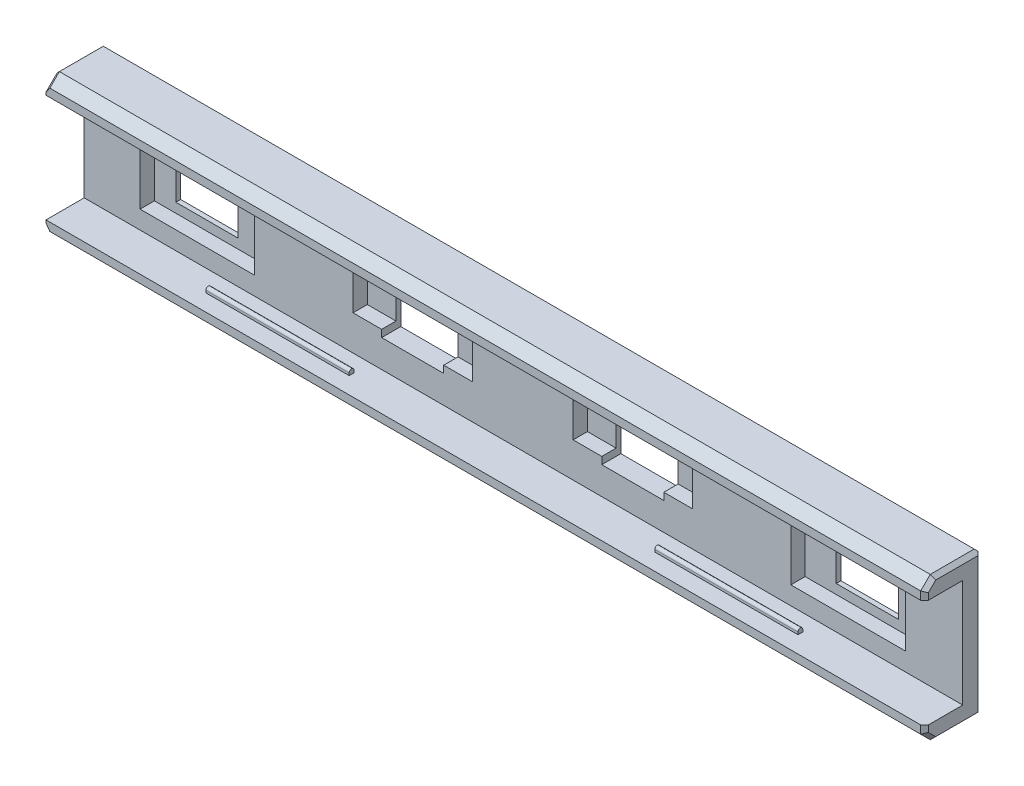
SolidWorks part; units mm, degrees
ref_plane "Front Plane" through (0, 0, 0) normal (0, 0, 1) x (1, 0, 0)
ref_plane "Top Plane" through (0, 0, 0) normal (0, 1, 0) x (1, 0, 0)
ref_plane "Right Plane" through (0, 0, 0) normal (1, 0, 0) x (0, 0, -1)
sketch "Sketch1" plane through (0, 0, 0) normal (0, 0, 1) x (1, 0, 0)
  line L1 (-45.75, 25.6543) -> (46.25, 25.6543)
  line L2 (-45.75, 25.6543) -> (-45.75, 10.6543)
  line L3 (-45.75, 10.6543) -> (46.25, 10.6543)
  line L4 (46.25, 25.6543) -> (46.25, 10.6543)
  dimension "D1" = 92
  dimension "D2" = 15
extrude "Boss-Extrude1" add sketch "Sketch1" along normal blind 6
sketch "Sketch2" plane through (0, 0, 6) normal (0, 0, 1) x (1, 0, 0)
  line L0 (-45.75, 25.6543) -> (-45.75, 10.6543) construction
  line L1 (-37.65, 20.9043) -> (-31.15, 20.9043)
  line L2 (-37.65, 20.9043) -> (-37.65, 15.4043)
  line L3 (-37.65, 15.4043) -> (-31.15, 15.4043)
  line L4 (-31.15, 20.9043) -> (-31.15, 15.4043)
  line L5 (46.25, 25.6543) -> (-45.75, 25.6543) construction
  dimension "D1" = 6.5
  dimension "D2" = 5.5
  dimension "D3" = 8.1
  dimension "D4" = 4.75
extrude "Cut-Extrude1" cut sketch "Sketch2" against normal through all both and the other way through all
sketch "Sketch3" plane through (0, 0, 6) normal (0, 0, 1) x (1, 0, 0)
  line L0 (-31.15, 15.4043) -> (-31.15, 20.9043) construction
  line L1 (-14.6, 20.9043) -> (-8.1, 20.9043)
  line L2 (-14.6, 20.9043) -> (-14.6, 15.4043)
  line L3 (-14.6, 15.4043) -> (-8.1, 15.4043)
  line L4 (-8.1, 20.9043) -> (-8.1, 15.4043)
  dimension "D1" = 6.5
  dimension "D2" = 5.5
  dimension "D3" = 16.55
extrude "Cut-Extrude2" cut sketch "Sketch3" against normal through all both and the other way through all
sketch "Sketch4" plane through (0, 0, 6) normal (0, 0, 1) x (1, 0, 0)
  line L0 (-8.1, 15.4043) -> (-8.1, 20.9043) construction
  line L1 (8.45, 20.9043) -> (14.95, 20.9043)
  line L2 (8.45, 20.9043) -> (8.45, 15.4043)
  line L3 (8.45, 15.4043) -> (14.95, 15.4043)
  line L4 (14.95, 20.9043) -> (14.95, 15.4043)
  line L5 (-45.75, 10.6543) -> (46.25, 10.6543) construction
  dimension "D1" = 6.5
  dimension "D2" = 5.5
  dimension "D3" = 16.55
  dimension "D4" = 4.75
extrude "Cut-Extrude3" cut sketch "Sketch4" against normal through all both and the other way through all
sketch "Sketch5" plane through (0, 0, 6) normal (0, 0, 1) x (1, 0, 0)
  line L0 (14.95, 15.4043) -> (14.95, 20.9043) construction
  line L1 (31.5, 20.9043) -> (38, 20.9043)
  line L2 (31.5, 20.9043) -> (31.5, 15.4043)
  line L3 (31.5, 15.4043) -> (38, 15.4043)
  line L4 (38, 20.9043) -> (38, 15.4043)
  dimension "D1" = 6.5
  dimension "D2" = 5.5
  dimension "D3" = 16.55
extrude "Cut-Extrude4" cut sketch "Sketch5" against normal through all both and the other way through all
sketch "Sketch8" plane through (0, 0, 6) normal (0, 0, 1) x (1, 0, 0)
  line L0 (-45.75, 25.6543) -> (-45.75, 10.6543) construction
  line L1 (46.25, 10.6543) -> (46.25, 25.6543) construction
  line L2 (-45.75, 23.8043) -> (46.25, 23.8043)
  line L3 (-45.75, 23.8043) -> (-45.75, 12.5043)
  line L4 (-45.75, 12.5043) -> (46.25, 12.5043)
  line L5 (46.25, 23.8043) -> (46.25, 12.5043)
  line L6 (46.25, 25.6543) -> (-45.75, 25.6543) construction
  dimension "D1" = 11.3
  dimension "D2" = 1.85
extrude "Cut-Extrude5" cut sketch "Sketch8" against normal blind 4 and the other way through all
sketch "Sketch9" plane through (0, 0, 2) normal (0, 0, 1) x (1, 0, 0)
  line L2 (46.25, 12.5043) -> (46.25, 23.8043) construction
  line L3 (28.25, 21.9043) -> (40.25, 21.9043)
  line L4 (28.25, 21.9043) -> (28.25, 14.4043)
  line L5 (28.25, 14.4043) -> (40.25, 14.4043)
  line L6 (40.25, 21.9043) -> (40.25, 14.4043)
  line L7 (-45.75, 12.5043) -> (46.25, 12.5043) construction
  line L11 (46.25, 12.5043) -> (-45.75, 12.5043) construction
  line L12 (-39.9, 21.9043) -> (-27.9, 21.9043)
  line L13 (-39.9, 21.9043) -> (-39.9, 14.4043)
  line L14 (-39.9, 14.4043) -> (-27.9, 14.4043)
  line L15 (-27.9, 21.9043) -> (-27.9, 14.4043)
  line L16 (-37.65, 15.4043) -> (-37.65, 20.9043) construction
  dimension "D1" = 6
  dimension "D2" = 12
  dimension "D3" = 7.5
  dimension "D4" = 1.9
  dimension "D5" = 12
  dimension "D6" = 7.5
  dimension "D7" = 1.9
  dimension "D8" = 2.25
extrude "Cut-Extrude6" cut sketch "Sketch9" against normal blind 1.5
sketch "Sketch10" plane through (0, 0, 2) normal (0, 0, 1) x (1, 0, 0)
  line L1 (5.45, 20.1543) -> (17.95, 20.1543)
  line L2 (5.45, 20.1543) -> (5.45, 16.1543)
  line L3 (5.45, 16.1543) -> (17.95, 16.1543)
  line L4 (17.95, 20.1543) -> (17.95, 16.1543)
  line L5 (-17.6, 20.1543) -> (-5.1, 20.1543)
  line L6 (-17.6, 20.1543) -> (-17.6, 16.1543)
  line L7 (-17.6, 16.1543) -> (-5.1, 16.1543)
  line L8 (-5.1, 20.1543) -> (-5.1, 16.1543)
  line L9 (-14.6, 15.4043) -> (-14.6, 20.9043) construction
  line L10 (-8.1, 20.9043) -> (-8.1, 15.4043) construction
  line L11 (-8.1, 15.4043) -> (-14.6, 15.4043) construction
  line L13 (8.45, 15.4043) -> (8.45, 20.9043) construction
  line L15 (14.95, 15.4043) -> (8.45, 15.4043) construction
  dimension "D1" = 3
  dimension "D2" = 3
  dimension "D3" = 4
  dimension "D4" = 0.75
  dimension "D5" = 12.5
  dimension "D6" = 3
  dimension "D7" = 4
  dimension "D8" = 0.75
extrude "Cut-Extrude7" cut sketch "Sketch10" against normal blind 1.5
sketch "Sketch12" plane through (46.25, 0, 0) normal (1, 0, 0) x (0, 0, -1)
  line L0 (-6, 25.6543) -> (-6, 24.6543)
  line L1 (-6, 23.8043) -> (-6, 25.6543) construction
  line L2 (-6, 24.6543) -> (-5, 25.6543)
  line L3 (-6, 25.6543) -> (0, 25.6543) construction
  line L4 (-5, 25.6543) -> (-6, 25.6543)
  line L5 (-6, 10.6543) -> (-5, 10.6543)
  line L6 (-6, 10.6543) -> (0, 10.6543) construction
  line L7 (-5, 10.6543) -> (-6, 11.6543)
  line L8 (-6, 10.6543) -> (-6, 12.5043) construction
  line L9 (-6, 11.6543) -> (-6, 10.6543)
  dimension "D1" = 1
  dimension "D2" = 1
  dimension "D3" = 1
extrude "Cut-Extrude8" cut sketch "Sketch12" against normal blind 92
sketch "Sketch13" plane through (0, 0, 0) normal (0, 0, -1) x (-1, 0, 0)
  line L0 (45.75, 25.6543) -> (45.75, 10.6543) construction
  line L1 (43.25, 23.1543) -> (43.75, 23.1543)
  line L2 (43.25, 23.1543) -> (43.25, 13.1543)
  line L3 (43.25, 13.1543) -> (43.75, 13.1543)
  line L4 (43.75, 23.1543) -> (43.75, 13.1543)
  line L5 (-46.25, 25.6543) -> (45.75, 25.6543) construction
  dimension "D1" = 2
  dimension "D2" = 0.5
  dimension "D3" = 10
  dimension "D4" = 2.5
extrude "Cut-Extrude9" cut sketch "Sketch13" against normal blind 0.6
fillet "Fillet1" radius 0.25 1 edges at (-43.75, 18.1543, 0)
fillet "Fillet2" radius 0.25 4 edges at (-43.5, 23.1543, 0.6) (-43.75, 18.1543, 0.6) (-43.5, 13.1543, 0.6) (-43.25, 18.1543, 0.6)
sketch "Sketch16" plane through (0, 23.8043, 0) normal (0, -1, 0) x (1, 0, 0)
  line L0 (-45.75, 6) -> (46.25, 6) construction
  line L1 (-15.75, 4.25) -> (-30.75, 4.25)
  line L2 (-15.75, 4.25) -> (-15.75, 3.75)
  line L3 (-15.75, 3.75) -> (-30.75, 3.75)
  line L4 (-30.75, 4.25) -> (-30.75, 3.75)
  line L5 (-45.75, 6) -> (-45.75, 2) construction
  dimension "D1" = 15
  dimension "D2" = 0.5
  dimension "D3" = 1.75
  dimension "D4" = 15
extrude "Boss-Extrude2" add sketch "Sketch16" along normal blind 0.75
fillet "Fillet3" radius 0.5 1 edges at (-23.25, 23.0543, 4.25)
fillet "Fillet4" radius 0.25 1 edges at (-23.25, 23.0543, 3.75)
sketch "Sketch17" plane through (0, 12.5043, 0) normal (0, 1, 0) x (1, 0, 0)
  line L0 (-45.75, -6) -> (-45.75, -2) construction
  line L1 (-15.75, -3.75) -> (-30.75, -3.75)
  line L2 (-15.75, -3.75) -> (-15.75, -4.25)
  line L3 (-15.75, -4.25) -> (-30.75, -4.25)
  line L4 (-30.75, -3.75) -> (-30.75, -4.25)
  line L5 (46.25, -6) -> (-45.75, -6) construction
  dimension "D1" = 15
  dimension "D2" = 0.5
  dimension "D3" = 15
  dimension "D4" = 1.75
extrude "Boss-Extrude3" add sketch "Sketch17" along normal blind 0.75
fillet "Fillet5" radius 0.5 1 edges at (-23.25, 13.2543, 4.25)
fillet "Fillet6" radius 0.25 1 edges at (-23.25, 13.2543, 3.75)
pattern_linear "LPattern1" count 2 spacing 47 along (1, 0, 0) of "Boss-Extrude3"
pattern_linear "LPattern2" count 2 spacing 47 along (1, 0, 0) of "Boss-Extrude2"
fillet "Fillet7" radius 0.5 1 edges at (23.75, 23.0543, 4.25)
fillet "Fillet8" radius 0.25 1 edges at (23.75, 23.0543, 3.75)
fillet "Fillet9" radius 0.5 1 edges at (23.75, 13.2543, 4.25)
fillet "Fillet10" radius 0.25 1 edges at (23.75, 13.2543, 3.75)
chamfer "Chamfer1" distance 0.4 angle 45 2 edges at (0.25, 10.6543, 0) (0.25, 25.6543, 0)
chamfer "Chamfer2" distance 0.4 angle 45 2 edges at (46.25, 18.1543, 0) (-45.75, 18.1543, 0)
chamfer "Chamfer3" distance 0.4 angle 45 2 edges at (-45.75, 10.6543, 2.7) (-45.75, 25.6543, 2.7)
chamfer "Chamfer4" distance 0.4 angle 45 2 edges at (-45.75, 11.3543, 5.7) (-45.75, 24.9543, 5.7)
chamfer "Chamfer5" distance 0.4 angle 45 6 edges at (46.25, 24.2293, 6) (46.25, 25.1543, 5.5) (46.25, 25.6543, 2.7) (46.25, 12.0793, 6) (46.25, 11.1543, 5.5) (46.25, 10.6543, 2.7)
